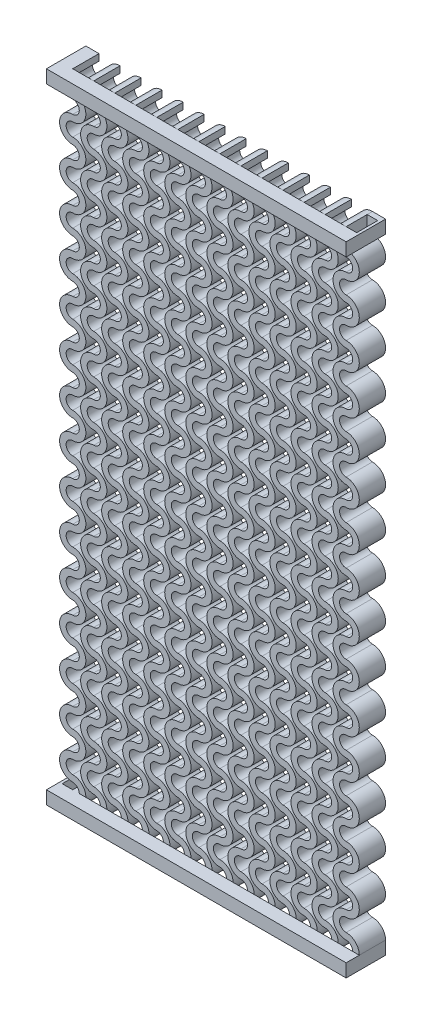
SolidWorks part; units mm, degrees
ref_plane "Front Plane" through (0, 0, 0) normal (0, 0, 1) x (1, 0, 0)
ref_plane "Top Plane" through (0, 0, 0) normal (0, 1, 0) x (1, 0, 0)
ref_plane "Right Plane" through (0, 0, 0) normal (1, 0, 0) x (0, 0, -1)
sketch "Sketch2" plane through (0, 0, 0) normal (0, 0, 1) x (1, 0, 0)
  line L0 (0, 0) -> (0, 8.4344) construction
  line L1 (0, -3.175) -> (0, -1.5875)
  line L4 (0, 150.8125) -> (0, 149.225)
  arc A0 (0, 3.175) -> (0, -3.175) centre (0, 0) cw
  arc A1 (0, 3.175) -> (0, 6.35) centre (0, 4.7625) cw
  arc A2 (0, 6.35) -> (0, 12.7) centre (0, 9.525) ccw
  arc A3 (0, 12.7) -> (0, 15.875) centre (0, 14.2875) cw
  arc A4 (0, 15.875) -> (0, 22.225) centre (0, 19.05) ccw
  arc A5 (0, 22.225) -> (0, 25.4) centre (0, 23.8125) cw
  arc A6 (0, 25.4) -> (0, 31.75) centre (0, 28.575) ccw
  arc A7 (0, 31.75) -> (0, 34.925) centre (0, 33.3375) cw
  arc A8 (0, 1.5875) -> (0, -1.5875) centre (0, 0) cw
  arc A9 (0, 1.5875) -> (0, 7.9375) centre (0, 4.7625) cw
  arc A10 (0, 7.9375) -> (0, 11.1125) centre (0, 9.525) ccw
  arc A11 (0, 11.1125) -> (0, 17.4625) centre (0, 14.2875) cw
  arc A12 (0, 17.4625) -> (0, 20.6375) centre (0, 19.05) ccw
  arc A13 (0, 20.6375) -> (0, 26.9875) centre (0, 23.8125) cw
  arc A14 (0, 26.9875) -> (0, 30.1625) centre (0, 28.575) ccw
  arc A15 (0, 30.1625) -> (0, 36.5125) centre (0, 33.3375) cw
  arc A16 (0, 41.275) -> (0, 44.45) centre (0, 42.8625) cw
  arc A17 (0, 36.5125) -> (0, 39.6875) centre (0, 38.1) ccw
  arc A18 (0, 34.925) -> (0, 41.275) centre (0, 38.1) ccw
  arc A19 (0, 39.6875) -> (0, 46.0375) centre (0, 42.8625) cw
  arc A20 (0, 74.6125) -> (0, 77.7875) centre (0, 76.2) ccw
  arc A21 (0, 50.8) -> (0, 44.45) centre (0, 47.625) cw
  arc A22 (0, 49.2125) -> (0, 55.5625) centre (0, 52.3875) cw
  arc A23 (0, 82.55) -> (0, 88.9) centre (0, 85.725) ccw
  arc A24 (0, 65.0875) -> (0, 68.2625) centre (0, 66.675) ccw
  arc A25 (0, 84.1375) -> (0, 87.3125) centre (0, 85.725) ccw
  arc A26 (0, 88.9) -> (0, 92.075) centre (0, 90.4875) cw
  arc A27 (0, 68.2625) -> (0, 74.6125) centre (0, 71.4375) cw
  arc A28 (0, 63.5) -> (0, 69.85) centre (0, 66.675) ccw
  arc A29 (0, 69.85) -> (0, 73.025) centre (0, 71.4375) cw
  arc A30 (0, 77.7875) -> (0, 84.1375) centre (0, 80.9625) cw
  arc A31 (0, 73.025) -> (0, 79.375) centre (0, 76.2) ccw
  arc A32 (0, 49.2125) -> (0, 46.0375) centre (0, 47.625) cw
  arc A33 (0, 50.8) -> (0, 53.975) centre (0, 52.3875) cw
  arc A34 (0, 55.5625) -> (0, 58.7375) centre (0, 57.15) ccw
  arc A35 (0, 60.325) -> (0, 63.5) centre (0, 61.9125) cw
  arc A36 (0, 79.375) -> (0, 82.55) centre (0, 80.9625) cw
  arc A37 (0, 87.3125) -> (0, 93.6625) centre (0, 90.4875) cw
  arc A38 (0, 53.975) -> (0, 60.325) centre (0, 57.15) ccw
  arc A39 (0, 58.7375) -> (0, 65.0875) centre (0, 61.9125) cw
  arc A40 (0, 134.9375) -> (0, 141.2875) centre (0, 138.1125) cw
  arc A41 (0, 115.8875) -> (0, 122.2375) centre (0, 119.0625) cw
  arc A42 (0, 127) -> (0, 130.175) centre (0, 128.5875) cw
  arc A43 (0, 107.95) -> (0, 111.125) centre (0, 109.5375) cw
  arc A44 (0, 136.525) -> (0, 139.7) centre (0, 138.1125) cw
  arc A45 (0, 96.8375) -> (0, 103.1875) centre (0, 100.0125) cw
  arc A46 (0, 130.175) -> (0, 136.525) centre (0, 133.35) ccw
  arc A47 (0, 120.65) -> (0, 127) centre (0, 123.825) ccw
  arc A48 (0, 103.1875) -> (0, 106.3625) centre (0, 104.775) ccw
  arc A49 (0, 98.425) -> (0, 92.075) centre (0, 95.25) cw
  arc A50 (0, 98.425) -> (0, 101.6) centre (0, 100.0125) cw
  arc A51 (0, 101.6) -> (0, 107.95) centre (0, 104.775) ccw
  arc A52 (0, 117.475) -> (0, 120.65) centre (0, 119.0625) cw
  arc A53 (0, 125.4125) -> (0, 131.7625) centre (0, 128.5875) cw
  arc A54 (0, 96.8375) -> (0, 93.6625) centre (0, 95.25) cw
  arc A55 (0, 106.3625) -> (0, 112.7125) centre (0, 109.5375) cw
  arc A56 (0, 122.2375) -> (0, 125.4125) centre (0, 123.825) ccw
  arc A57 (0, 131.7625) -> (0, 134.9375) centre (0, 133.35) ccw
  arc A58 (0, 112.7125) -> (0, 115.8875) centre (0, 114.3) ccw
  arc A59 (0, 111.125) -> (0, 117.475) centre (0, 114.3) ccw
  arc A60 (0, 146.05) -> (0, 139.7) centre (0, 142.875) cw
  arc A61 (0, 146.05) -> (0, 149.225) centre (0, 147.6375) cw
  arc A62 (0, 144.4625) -> (0, 141.2875) centre (0, 142.875) cw
  arc A63 (0, 144.4625) -> (0, 150.8125) centre (0, 147.6375) cw
  dimension "D1" = 3.175
  dimension "D2" = 1.5875
  dimension "D5" = 1.5875
  dimension "D7" = 3.175
  dimension "D8" = 1.5875
  dimension "D9" = 3.175
  dimension "D10" = 3.175
  dimension "D4" = 9.525
  dimension "D6" = 9.525
  dimension "D3" = 1.5875
extrude "Boss-Extrude1" add sketch "Sketch2" along normal blind 6.35
pattern_linear "LPattern1" count 14 spacing 5.08 along (1, 0, 0) of bodies 101
sketch "Sketch5" plane through (66.04, 0, 0) normal (1, 0, 0) x (0, 0, -1)
  line L1 (-6.35, 150.8125) -> (-9.525, 150.8125)
  line L2 (-6.35, 150.8125) -> (-6.35, 147.6375)
  line L3 (-6.35, 147.6375) -> (-9.525, 147.6375)
  line L4 (-9.525, 150.8125) -> (-9.525, 147.6375)
  dimension "D1" = 3.175
  dimension "D2" = 3.175
extrude "Boss-Extrude2" add sketch "Sketch5" against normal through all
sketch "Sketch6" plane through (0, 0, 0) normal (-1, 0, 0) x (0, 0, 1)
  line L1 (6.35, -3.175) -> (9.525, -3.175)
  line L2 (6.35, -3.175) -> (6.35, 0)
  line L3 (6.35, 0) -> (9.525, 0)
  line L4 (9.525, -3.175) -> (9.525, 0)
  dimension "D1" = 3.175
  dimension "D2" = 3.175
extrude "Boss-Extrude3" add sketch "Sketch6" against normal through all
sketch "Sketch8" plane through (0, 0, 6.35) normal (0, 0, -1) x (-1, 0, 0)
  line L0 (-66.04, 147.6375) -> (-64.4525, 147.6375) construction
  line L1 (-66.04, 149.225) -> (-66.04, 147.6375) construction
  line L2 (3.175, 147.6375) -> (3.175, 150.8125) construction
  line L3 (3.175, 150.8125) -> (0, 150.8125) construction
  line L4 (0, -1.5875) -> (0, 0) construction
  line L5 (0, 0) -> (-1.5875, 0) construction
  line L6 (-69.215, 0) -> (-69.215, -3.175) construction
  line L7 (-69.215, -3.175) -> (-66.04, -3.175) construction
  line L8 (-66.04, 147.6375) -> (-64.4525, 147.6375)
  line L9 (-66.04, 149.225) -> (-66.04, 147.6375)
  line L10 (3.175, 147.6375) -> (3.175, 150.8125)
  line L11 (3.175, 150.8125) -> (0, 150.8125)
  line L12 (0, -1.5875) -> (0, 0)
  line L13 (0, 0) -> (-1.5875, 0)
  line L14 (-69.215, 0) -> (-69.215, -3.175)
  line L15 (-69.215, -3.175) -> (-66.04, -3.175)
  arc A0 (-64.4525, 147.6375) -> (-66.04, 149.225) centre (-66.04, 147.6375) ccw construction
  arc A1 (3.175, 147.6375) -> (0, 150.8125) centre (0, 147.6375) ccw construction
  arc A2 (-1.5875, 0) -> (0, -1.5875) centre (0, 0) ccw construction
  arc A3 (-69.215, 0) -> (-66.04, -3.175) centre (-66.04, 0) ccw construction
  arc A4 (-64.4525, 147.6375) -> (-66.04, 149.225) centre (-66.04, 147.6375) ccw
  arc A5 (3.175, 147.6375) -> (0, 150.8125) centre (0, 147.6375) ccw
  arc A6 (-1.5875, 0) -> (0, -1.5875) centre (0, 0) ccw
  arc A7 (-69.215, 0) -> (-66.04, -3.175) centre (-66.04, 0) ccw
extrude "Boss-Extrude5" add sketch "Sketch8" along normal through all
sketch "Sketch9" plane through (0, 0, 0) normal (-1, 0, 0) x (0, 0, 1)
  line L5 (9.525, 0) -> (0, 0)
  line L6 (0, 0) -> (0, -3.175)
  line L7 (0, -3.175) -> (6.35, -3.175)
  line L8 (6.35, -3.175) -> (9.525, -3.175)
  line L9 (9.525, -3.175) -> (9.525, 0)
  line L10 (9.525, 0) -> (0, 0)
  line L11 (0, 0) -> (0, -3.175)
  line L12 (0, -3.175) -> (6.35, -3.175)
  line L13 (6.35, -3.175) -> (9.525, -3.175)
  line L14 (9.525, -3.175) -> (9.525, 0)
  dimension "D1" = 0
extrude "Boss-Extrude6" add sketch "Sketch9" along normal through all
sketch "Sketch10" plane through (66.04, 0, 0) normal (1, 0, 0) x (0, 0, -1)
  line L5 (-9.525, 147.6375) -> (0, 147.6375)
  line L6 (0, 147.6375) -> (0, 150.8125)
  line L7 (0, 150.8125) -> (-6.35, 150.8125)
  line L8 (-6.35, 150.8125) -> (-9.525, 150.8125)
  line L9 (-9.525, 150.8125) -> (-9.525, 147.6375)
  line L10 (-9.525, 147.6375) -> (0, 147.6375)
  line L11 (0, 147.6375) -> (0, 150.8125)
  line L12 (0, 150.8125) -> (-6.35, 150.8125)
  line L13 (-6.35, 150.8125) -> (-9.525, 150.8125)
  line L14 (-9.525, 150.8125) -> (-9.525, 147.6375)
  dimension "D1" = 0
extrude "Boss-Extrude7" add sketch "Sketch10" along normal through all
sketch "Sketch11" plane through (0, 150.8125, 0) normal (0, 1, 0) x (1, 0, 0)
  line L0 (69.215, 0) -> (66.04, 0) construction
  line L1 (66.04, -6.35) -> (68.58, -6.35)
  line L2 (66.04, -6.35) -> (66.04, -1.27)
  line L3 (66.04, -1.27) -> (68.58, -1.27)
  line L4 (68.58, -6.35) -> (68.58, -1.27)
  dimension "D1" = 2.54
  dimension "D2" = 1.27
extrude "Cut-Extrude1" cut sketch "Sketch11" against normal up to next
sketch "Sketch12" plane through (0, -3.175, 0) normal (0, -1, 0) x (1, 0, 0)
  line L0 (-3.175, 0) -> (0, 0) construction
  line L1 (0, 6.35) -> (-2.54, 6.35)
  line L2 (0, 6.35) -> (0, 1.27)
  line L3 (0, 1.27) -> (-2.54, 1.27)
  line L4 (-2.54, 6.35) -> (-2.54, 1.27)
  dimension "D1" = 2.54
  dimension "D2" = 1.27
extrude "Cut-Extrude2" cut sketch "Sketch12" against normal up to next
